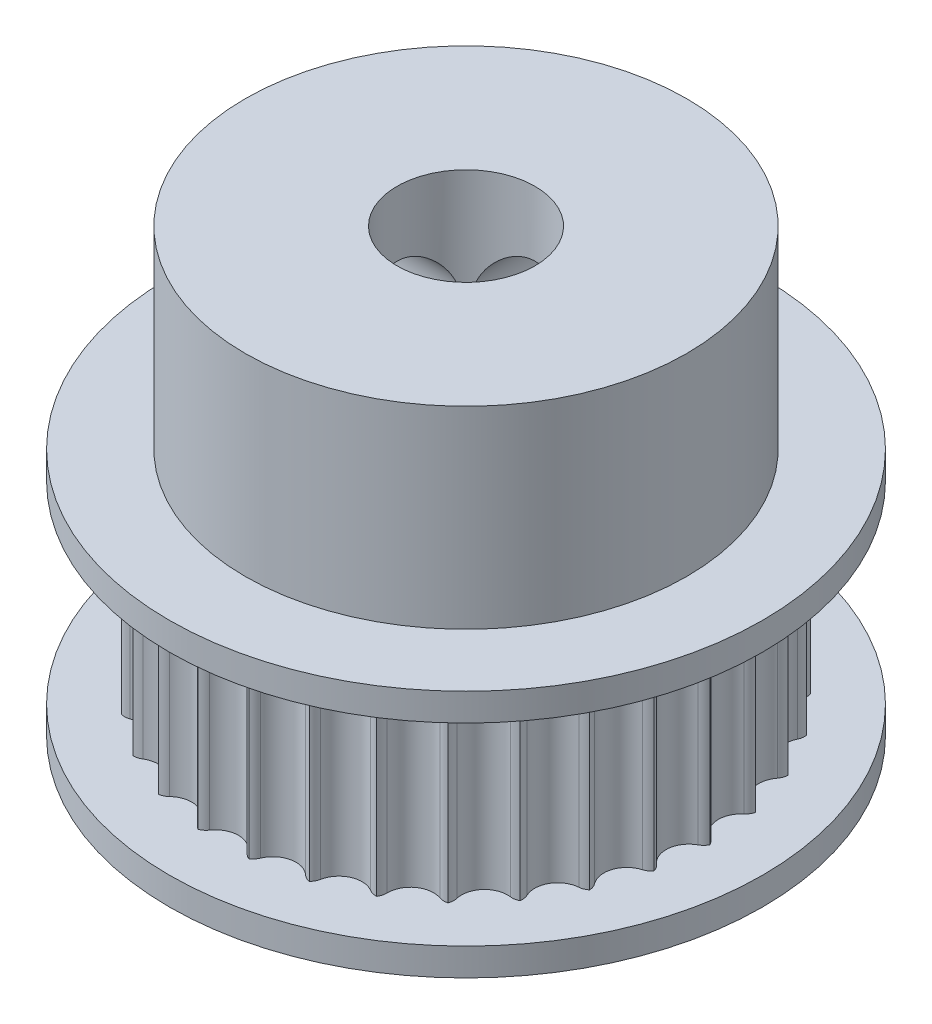
SolidWorks part; units mm, degrees
ref_plane "Front plan" through (0, 0, 0) normal (0, 0, 1) x (1, 0, 0)
ref_plane "Top plan" through (0, 0, 0) normal (0, 1, 0) x (1, 0, 0)
ref_plane "Right plan" through (0, 0, 0) normal (1, 0, 0) x (0, 0, -1)
sketch "Skica2" plane through (0, 0, 0) normal (0, 0, 1) x (1, 0, 0)
  line L0 (8, 8.5) -> (2.5, 8.5)
  line L1 (2.5, 8.5) -> (2.5, -8.5)
  line L2 (2.5, -8.5) -> (6.11, -8.5)
  line L3 (0, -8.5) -> (0, 8.5) construction
  line L4 (0, 8.5) -> (2.5, 8.5)
  line L5 (0, -8.5) -> (2.5, -8.5)
  line L6 (6.11, -8.5) -> (6.11, -7.5)
  line L7 (10.75, 0.5) -> (9.25, 0.5)
  line L8 (9.25, 0.5) -> (9.25, -6.5)
  line L9 (10.75, 0.5) -> (10.75, 1.5)
  line L12 (10.75, -7.5) -> (6.11, -7.5)
  line L13 (10.75, 1.5) -> (8, 1.5)
  line L14 (10.75, -7.5) -> (10.75, -6.5)
  line L15 (9.25, -6.5) -> (10.75, -6.5)
  line L16 (8, 1.5) -> (8, 8.5)
  point P2 (9.25, 0.5)
  point P6 (8.43, -7.5)
  point P7 (0, 0)
  point P17 (7.2212, 1.2408)
  dimension "D3" = 18.5
  dimension "D1" = 5
  dimension "D2" = 1
  dimension "D4" = 1
  dimension "D6" = 21.5
  dimension "D7" = 16
  dimension "D8" = 17
  dimension "D9" = 7
revolve "Revolute" add sketch "Skica2" angle 360 about L3 region at (5.7111, -0.261, 0)
sketch "Sketch2" plane through (0, 0.5, 0) normal (0, -1, 0) x (1, 0, 0)
  line L0 (0, 0) -> (0, 9.0829) construction
  line L1 (0, 0) -> (3.0348, 8.4729) construction
  line L3 (0, 0) -> (-1.6132, 8.7491) construction
  circle A1 centre (0, 0) radius 8.2469 construction
  circle A2 centre (0, 0) radius 8.6357 construction
  arc A3 (-0.6881, 8.6082) -> (0.6881, 8.6082) centre (0, 9.0829) ccw
  arc A7 (-1.1652, 8.82) -> (-1.6132, 8.7491) centre (0, 0) ccw
  arc A8 (0, 10.1685) -> (1.6132, 8.7491) centre (0.3953, 8.9913) cw
  circle A9 centre (0, 0) radius 9 construction
  arc A10 (1.1652, 8.82) -> (1.6132, 8.7491) centre (0, 0) cw
  arc A11 (1.1652, 8.82) -> (0.6881, 8.6082) centre (1.0997, 8.3243) ccw
  arc A12 (0, 10.1685) -> (-1.6132, 8.7491) centre (-0.3953, 8.9913) ccw
  arc A13 (-1.1652, 8.82) -> (-0.6881, 8.6082) centre (-1.0997, 8.3243) cw
  point P0 (-1.0997, 8.3243)
  point P5 (0, 6.1378)
  point P8 (0, 0)
  circle M8 centre (0, 0) radius 9.25
  dimension "D2" = 1
  dimension "D3" = 1.2417
  dimension "D4" = 0.836
  dimension "D6" = 18
extrude "Cut-Extrude1" cut sketch "Sketch2" along normal up to surface (7 mm away) contours A8 M8 | A11 A3 M8 region at (0, 0.5, 8.8612) region at (0, 0.5, 9.6545) up to face at (10.75, -6.5, 0)
pattern_circular "CirPattern1" count 30 over 360 about axis through (0, -8.5, 0) along (0, -1, 0) of "Cut-Extrude1" reverse direction yes
sketch "Sketch3" plane through (0, 0, 0) normal (1, 0, 0) x (0, 0, -1)
  line L0 (0, 8.5) -> (0, 0.5) construction
  line L1 (2.5, 8.5) -> (-2.5, 8.5) construction
  circle A0 centre (0, 4.5) radius 1.65
  point P8 (0, 0)
  dimension "D1" = 3.3
extrude "Cut-Extrude2" cut sketch "Sketch3" against normal up to next
sketch "Sketch4" plane through (0, 0, 0) normal (0, 0, 1) x (1, 0, 0)
  line L0 (0, 8.5) -> (0, 0.5) construction
  line L1 (10.75, 8.5) -> (-10.75, 8.5) construction
  line L2 (-0.6881, 0.5) -> (0.6881, 0.5) construction
  circle A0 centre (0, 4.5) radius 1.65
  dimension "D1" = 3.3
extrude "Cut-Extrude3" cut sketch "Sketch4" against normal up to next
chamfer "Chamfer1" distance 1 angle 45 1 edges at (6.11, -7.5, 0)
equation "\"`\"=2"
